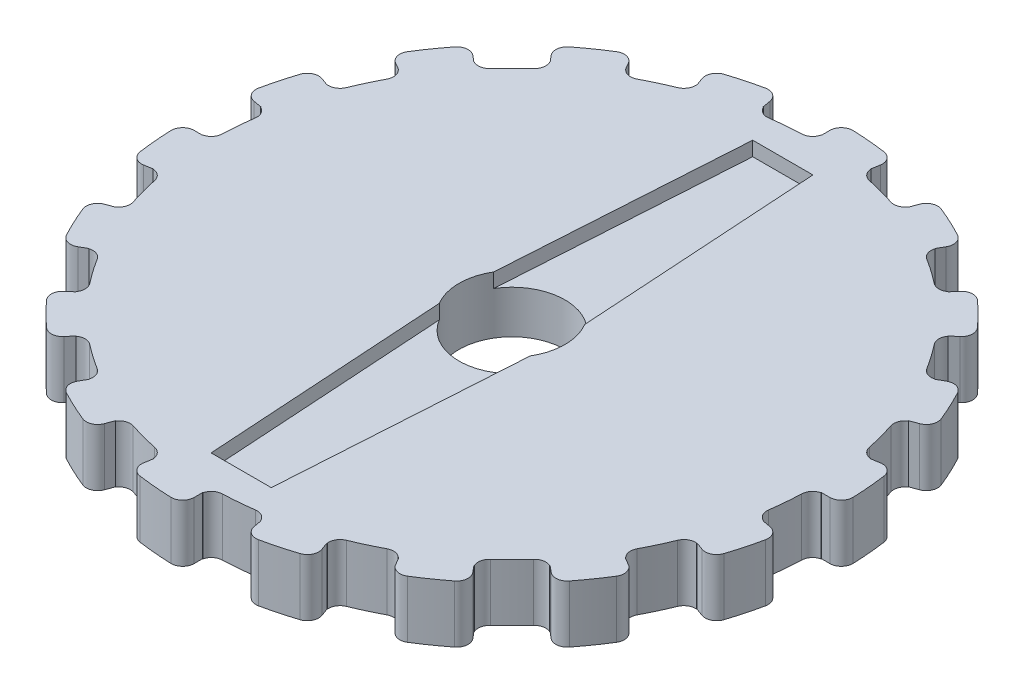
SolidWorks part; units mm, degrees
material "PLA"
ref_plane "Alzado" through (0, 0, 0) normal (0, 0, 1) x (1, 0, 0)
ref_plane "Planta" through (0, 0, 0) normal (0, 1, 0) x (1, 0, 0)
ref_plane "Vista lateral" through (0, 0, 0) normal (1, 0, 0) x (0, 0, -1)
sketch "Croquis1" plane through (0, 0, 0) normal (0, 1, 0) x (1, 0, 0)
  line L0 (0, 0) -> (0, 24) construction
  line L1 (0, 0) -> (4.1676, 23.6354) construction
  line L2 (0, 0) -> (8.2085, 22.5526) construction
  line L3 (0, 0) -> (12, 20.7846) construction
  line L4 (0, 0) -> (15.4269, 18.3851) construction
  line L5 (0, 0) -> (18.3851, 15.4269) construction
  line L6 (0, 0) -> (20.7846, 12) construction
  line L7 (0, 0) -> (22.5526, 8.2085) construction
  line L8 (0, 0) -> (23.6354, 4.1676) construction
  line L9 (0, 0) -> (24, 0) construction
  line L10 (0, 0) -> (23.6354, -4.1676) construction
  line L11 (0, 0) -> (22.5526, -8.2085) construction
  line L12 (0, 0) -> (20.7846, -12) construction
  line L13 (0, 0) -> (18.3851, -15.4269) construction
  line L14 (0, 0) -> (15.4269, -18.3851) construction
  line L15 (0, 0) -> (12, -20.7846) construction
  line L16 (0, 0) -> (8.2085, -22.5526) construction
  line L17 (0, 0) -> (4.1676, -23.6354) construction
  line L18 (0, 0) -> (0, -24) construction
  line L19 (0, 0) -> (-4.1676, -23.6354) construction
  line L20 (0, 0) -> (-8.2085, -22.5526) construction
  line L21 (0, 0) -> (-12, -20.7846) construction
  line L22 (0, 0) -> (-15.4269, -18.3851) construction
  line L23 (0, 0) -> (-18.3851, -15.4269) construction
  line L24 (0, 0) -> (-20.7846, -12) construction
  line L25 (0, 0) -> (-22.5526, -8.2085) construction
  line L26 (0, 0) -> (-23.6354, -4.1676) construction
  line L27 (0, 0) -> (-24, 0) construction
  line L28 (0, 0) -> (-23.6354, 4.1676) construction
  line L29 (0, 0) -> (-22.5526, 8.2085) construction
  line L30 (0, 0) -> (-20.7846, 12) construction
  line L31 (0, 0) -> (-18.3851, 15.4269) construction
  line L32 (0, 0) -> (-15.4269, 18.3851) construction
  line L33 (0, 0) -> (-12, 20.7846) construction
  line L34 (0, 0) -> (-8.2085, 22.5526) construction
  line L35 (0, 0) -> (-4.1676, 23.6354) construction
  line L36 (4.1676, 23.6354) -> (3.7508, 21.2718)
  line L37 (7.3876, 20.2974) -> (8.2085, 22.5526)
  line L38 (12, 20.7846) -> (10.8, 18.7061)
  line L39 (13.8842, 16.5466) -> (15.4269, 18.3851)
  line L40 (18.3851, 15.4269) -> (16.5466, 13.8842)
  line L41 (18.7061, 10.8) -> (20.7846, 12)
  line L42 (22.5526, 8.2085) -> (20.2974, 7.3876)
  line L43 (21.2718, 3.7508) -> (23.6354, 4.1676)
  line L44 (24, 0) -> (21.6, 0)
  line L45 (21.2718, -3.7508) -> (23.6354, -4.1676)
  line L46 (22.5526, -8.2085) -> (20.2974, -7.3876)
  line L47 (18.7061, -10.8) -> (20.7846, -12)
  line L48 (18.3851, -15.4269) -> (16.5466, -13.8842)
  line L49 (13.8842, -16.5466) -> (15.4269, -18.3851)
  line L50 (12, -20.7846) -> (10.8, -18.7061)
  line L51 (7.3876, -20.2974) -> (8.2085, -22.5526)
  line L52 (4.1676, -23.6354) -> (3.7508, -21.2718)
  line L53 (0, -21.6) -> (0, -24)
  line L54 (-4.1676, -23.6354) -> (-3.7508, -21.2718)
  line L55 (-7.3876, -20.2974) -> (-8.2085, -22.5526)
  line L56 (-12, -20.7846) -> (-10.8, -18.7061)
  line L57 (-13.8842, -16.5466) -> (-15.4269, -18.3851)
  line L58 (-18.3851, -15.4269) -> (-16.5466, -13.8842)
  line L59 (-18.7061, -10.8) -> (-20.7846, -12)
  line L60 (-22.5526, -8.2085) -> (-20.2974, -7.3876)
  line L61 (-21.2718, -3.7508) -> (-23.6354, -4.1676)
  line L62 (-24, 0) -> (-21.6, 0)
  line L63 (-21.2718, 3.7508) -> (-23.6354, 4.1676)
  line L64 (-22.5526, 8.2085) -> (-20.2974, 7.3876)
  line L65 (-18.7061, 10.8) -> (-20.7846, 12)
  line L66 (-18.3851, 15.4269) -> (-16.5466, 13.8842)
  line L67 (-13.8842, 16.5466) -> (-15.4269, 18.3851)
  line L68 (-12, 20.7846) -> (-10.8, 18.7061)
  line L69 (-7.3876, 20.2974) -> (-8.2085, 22.5526)
  line L70 (-4.1676, 23.6354) -> (-3.7508, 21.2718)
  line L71 (0, 21.6) -> (0, 24)
  circle A1 centre (0, 0) radius 3.7
  arc A2 (0, 24) -> (4.1676, 23.6354) centre (0, 0) cw
  arc A4 (3.7508, 21.2718) -> (7.3876, 20.2974) centre (0, 0) cw
  arc A5 (8.2085, 22.5526) -> (12, 20.7846) centre (0, 0) cw
  arc A6 (10.8, 18.7061) -> (13.8842, 16.5466) centre (0, 0) cw
  arc A7 (15.4269, 18.3851) -> (18.3851, 15.4269) centre (0, 0) cw
  arc A8 (16.5466, 13.8842) -> (18.7061, 10.8) centre (0, 0) cw
  arc A9 (20.7846, 12) -> (22.5526, 8.2085) centre (0, 0) cw
  arc A10 (20.2974, 7.3876) -> (21.2718, 3.7508) centre (0, 0) cw
  arc A11 (23.6354, 4.1676) -> (24, 0) centre (0, 0) cw
  arc A12 (21.6, 0) -> (21.2718, -3.7508) centre (0, 0) cw
  arc A13 (23.6354, -4.1676) -> (22.5526, -8.2085) centre (0, 0) cw
  arc A14 (20.2974, -7.3876) -> (18.7061, -10.8) centre (0, 0) cw
  arc A15 (20.7846, -12) -> (18.3851, -15.4269) centre (0, 0) cw
  arc A16 (16.5466, -13.8842) -> (13.8842, -16.5466) centre (0, 0) cw
  arc A17 (15.4269, -18.3851) -> (12, -20.7846) centre (0, 0) cw
  arc A18 (10.8, -18.7061) -> (7.3876, -20.2974) centre (0, 0) cw
  arc A19 (8.2085, -22.5526) -> (4.1676, -23.6354) centre (0, 0) cw
  arc A20 (3.7508, -21.2718) -> (0, -21.6) centre (0, 0) cw
  arc A21 (0, -24) -> (-4.1676, -23.6354) centre (0, 0) cw
  arc A22 (-3.7508, -21.2718) -> (-7.3876, -20.2974) centre (0, 0) cw
  arc A23 (-8.2085, -22.5526) -> (-12, -20.7846) centre (0, 0) cw
  arc A24 (-10.8, -18.7061) -> (-13.8842, -16.5466) centre (0, 0) cw
  arc A25 (-15.4269, -18.3851) -> (-18.3851, -15.4269) centre (0, 0) cw
  arc A26 (-16.5466, -13.8842) -> (-18.7061, -10.8) centre (0, 0) cw
  arc A27 (-20.7846, -12) -> (-22.5526, -8.2085) centre (0, 0) cw
  arc A28 (-20.2974, -7.3876) -> (-21.2718, -3.7508) centre (0, 0) cw
  arc A29 (-23.6354, -4.1676) -> (-24, 0) centre (0, 0) cw
  arc A30 (-21.6, 0) -> (-21.2718, 3.7508) centre (0, 0) cw
  arc A31 (-23.6354, 4.1676) -> (-22.5526, 8.2085) centre (0, 0) cw
  arc A32 (-20.2974, 7.3876) -> (-18.7061, 10.8) centre (0, 0) cw
  arc A33 (-20.7846, 12) -> (-18.3851, 15.4269) centre (0, 0) cw
  arc A34 (-16.5466, 13.8842) -> (-13.8842, 16.5466) centre (0, 0) cw
  arc A35 (-15.4269, 18.3851) -> (-12, 20.7846) centre (0, 0) cw
  arc A36 (-10.8, 18.7061) -> (-7.3876, 20.2974) centre (0, 0) cw
  arc A37 (-8.2085, 22.5526) -> (-4.1676, 23.6354) centre (0, 0) cw
  arc A38 (-3.7508, 21.2718) -> (0, 21.6) centre (0, 0) cw
  point P44 (0, 0)
  point P131 (0, 0)
  dimension "D1" = 10
  dimension "D3" = 18
  dimension "D2" = 18
extrude "Saliente-Extruir1" add sketch "Croquis1" along normal blind 4 contours A38 L70 A37 L69 A36 L68 A35 L67 A34 L66 A33 L65 A32 L64 A31 L63 A30 L62 A29 L61 A28 L60 A27 L59 A26 L58 A25 L57 A24 L56 A23 L55 A22 L54 A21 L53 A20 L52 A19 L51 A18 L50 A17 L49 A16 L48 A15 L47 A14 L46 A13 region at (3.2907, 0, -22.5715)
sketch "Croquis2" plane through (0, 4, 0) normal (0, 1, 0) x (1, 0, 0)
  line L0 (0, 1.9) -> (3.1749, 1.9) construction
  line L1 (-2.1, 18.9) -> (2.1, 18.9)
  line L2 (0, 0) -> (0, 1.9) construction
  line L3 (3.1749, 1.9) -> (2.1, 18.9)
  line L4 (0, 18.9) -> (0, 1.9) construction
  line L5 (-3.1749, 1.9) -> (-2.1, 18.9)
  line L6 (-2.2, 0) -> (2.2, 0) construction
  line L7 (3.1749, -1.9) -> (2.1, -18.9)
  line L8 (-2.1, -18.9) -> (2.1, -18.9)
  line L9 (-3.1749, -1.9) -> (-2.1, -18.9)
  circle A0 centre (0, 0) radius 3.7 construction
  arc A1 (3.1749, 1.9) -> (-3.1749, 1.9) centre (0, 0) ccw
  arc A2 (3.1749, -1.9) -> (-3.1749, -1.9) centre (0, 0) cw
extrude "Cortar-Extruir1" cut sketch "Croquis2" against normal blind 1
sketch "Croquis3" plane through (0, 4, 0) normal (0, 1, 0) x (1, 0, 0)
  line L0 (0, 22.1856) -> (0, 21) construction
  line L1 (3.8525, 21.8485) -> (3.783, 21.4543)
  line L2 (4.1676, 23.6354) -> (3.7508, 21.2718) construction
  line L3 (7.8665, 21.6129) -> (7.451, 20.4715) construction
  line L4 (7.3876, 20.2974) -> (8.2085, 22.5526) construction
  line L5 (7.451, 20.4715) -> (7.5879, 20.8476)
  line L6 (11.0928, 19.2133) -> (10.8927, 18.8666)
  line L7 (14.0033, 16.6885) -> (14.2606, 16.9951)
  line L8 (16.9951, 14.2606) -> (16.6885, 14.0033)
  line L9 (18.8666, 10.8927) -> (19.2133, 11.0928)
  line L10 (20.8476, 7.5879) -> (20.4715, 7.451)
  line L11 (21.4543, 3.783) -> (21.8485, 3.8525)
  line L12 (22.1856, 0) -> (21.7853, 0)
  line L13 (21.4543, -3.783) -> (21.8485, -3.8525)
  line L14 (20.8476, -7.5879) -> (20.4715, -7.451)
  line L15 (18.8666, -10.8927) -> (19.2133, -11.0928)
  line L16 (16.9951, -14.2606) -> (16.6885, -14.0033)
  line L17 (14.0033, -16.6885) -> (14.2606, -16.9951)
  line L18 (11.0928, -19.2133) -> (10.8927, -18.8666)
  line L19 (7.451, -20.4715) -> (7.5879, -20.8476)
  line L20 (3.8525, -21.8485) -> (3.783, -21.4543)
  line L21 (0, -21.7853) -> (0, -22.1856)
  line L22 (-3.8525, -21.8485) -> (-3.783, -21.4543)
  line L23 (-7.451, -20.4715) -> (-7.5879, -20.8476)
  line L24 (-11.0928, -19.2133) -> (-10.8927, -18.8666)
  line L25 (-14.0033, -16.6885) -> (-14.2606, -16.9951)
  line L26 (-16.9951, -14.2606) -> (-16.6885, -14.0033)
  line L27 (-18.8666, -10.8927) -> (-19.2133, -11.0928)
  line L28 (-20.8476, -7.5879) -> (-20.4715, -7.451)
  line L29 (-21.4543, -3.783) -> (-21.8485, -3.8525)
  line L30 (-22.1856, 0) -> (-21.7853, 0)
  line L31 (-21.4543, 3.783) -> (-21.8485, 3.8525)
  line L32 (-20.8476, 7.5879) -> (-20.4715, 7.451)
  line L33 (-18.8666, 10.8927) -> (-19.2133, 11.0928)
  line L34 (-16.9951, 14.2606) -> (-16.6885, 14.0033)
  line L35 (-14.0033, 16.6885) -> (-14.2606, 16.9951)
  line L36 (-11.0928, 19.2133) -> (-10.8927, 18.8666)
  line L37 (-7.451, 20.4715) -> (-7.5879, 20.8476)
  line L38 (-3.8525, 21.8485) -> (-3.783, 21.4543)
  line L39 (0, 21.7853) -> (0, 22.1856)
  line L40 (0, 22.1856) -> (0, 24)
  line L41 (4.1676, 23.6354) -> (3.8525, 21.8485)
  line L42 (7.5879, 20.8476) -> (8.2085, 22.5526)
  line L43 (12, 20.7846) -> (11.0928, 19.2133)
  line L44 (14.2606, 16.9951) -> (15.4269, 18.3851)
  line L45 (18.3851, 15.4269) -> (16.9951, 14.2606)
  line L46 (19.2133, 11.0928) -> (20.7846, 12)
  line L47 (22.5526, 8.2085) -> (20.8476, 7.5879)
  line L48 (21.8485, 3.8525) -> (23.6354, 4.1676)
  line L49 (24, 0) -> (22.1856, 0)
  line L50 (21.8485, -3.8525) -> (23.6354, -4.1676)
  line L51 (22.5526, -8.2085) -> (20.8476, -7.5879)
  line L52 (19.2133, -11.0928) -> (20.7846, -12)
  line L53 (18.3851, -15.4269) -> (16.9951, -14.2606)
  line L54 (14.2606, -16.9951) -> (15.4269, -18.3851)
  line L55 (12, -20.7846) -> (11.0928, -19.2133)
  line L56 (7.5879, -20.8476) -> (8.2085, -22.5526)
  line L57 (4.1676, -23.6354) -> (3.8525, -21.8485)
  line L58 (0, -22.1856) -> (0, -24)
  line L59 (-4.1676, -23.6354) -> (-3.8525, -21.8485)
  line L60 (-7.5879, -20.8476) -> (-8.2085, -22.5526)
  line L61 (-12, -20.7846) -> (-11.0928, -19.2133)
  line L62 (-14.2606, -16.9951) -> (-15.4269, -18.3851)
  line L63 (-18.3851, -15.4269) -> (-16.9951, -14.2606)
  line L64 (-19.2133, -11.0928) -> (-20.7846, -12)
  line L65 (-22.5526, -8.2085) -> (-20.8476, -7.5879)
  line L66 (-21.8485, -3.8525) -> (-23.6354, -4.1676)
  line L67 (-24, 0) -> (-22.1856, 0)
  line L68 (-21.8485, 3.8525) -> (-23.6354, 4.1676)
  line L69 (-22.5526, 8.2085) -> (-20.8476, 7.5879)
  line L70 (-19.2133, 11.0928) -> (-20.7846, 12)
  line L71 (-18.3851, 15.4269) -> (-16.9951, 14.2606)
  line L72 (-14.2606, 16.9951) -> (-15.4269, 18.3851)
  line L73 (-12, 20.7846) -> (-11.0928, 19.2133)
  line L74 (-7.5879, 20.8476) -> (-8.2085, 22.5526)
  line L75 (-4.1676, 23.6354) -> (-3.8525, 21.8485)
  circle A0 centre (0, 0) radius 23 construction
  circle A1 centre (0, 0) radius 21 construction
  arc A2 (0.8288, 22.9851) -> (3.1751, 22.7798) centre (0, 0) cw
  arc A3 (4.4031, 20.5332) -> (6.4534, 19.9838) centre (0, 0) cw
  arc A4 (7.451, 20.4715) -> (6.4534, 19.9838) centre (6.6993, 20.7451) cw
  arc A5 (3.783, 21.4543) -> (4.4031, 20.5332) centre (4.5708, 21.3154) ccw
  arc A6 (3.8525, 21.8485) -> (3.1751, 22.7798) centre (3.0646, 21.9875) ccw
  arc A7 (0, 22.1856) -> (0.8288, 22.9851) centre (0.8, 22.1856) cw
  arc A8 (8.6402, 21.3154) -> (11.506, 19.9151) centre (0, 0) cw construction
  arc A9 (7.5879, 20.8476) -> (8.6402, 21.3154) centre (8.3397, 20.574) cw construction
  arc A10 (7.5879, 20.8476) -> (8.6402, 21.3154) centre (8.3397, 20.574) cw
  arc A11 (8.6402, 21.3154) -> (10.7747, 20.3201) centre (0, 0) cw
  arc A12 (11.0928, 19.2133) -> (10.7747, 20.3201) centre (10.4, 19.6133) ccw
  arc A13 (10.8927, 18.8666) -> (11.1603, 17.789) centre (11.5855, 18.4666) ccw
  arc A14 (11.1603, 17.789) -> (12.8991, 16.5715) centre (0, 0) cw
  arc A15 (14.0033, 16.6885) -> (12.8991, 16.5715) centre (13.3905, 17.2028) cw
  arc A16 (14.2606, 16.9951) -> (15.4094, 17.0748) centre (14.8735, 16.4809) cw
  arc A17 (15.4094, 17.0748) -> (17.0748, 15.4094) centre (0, 0) cw
  arc A18 (16.9951, 14.2606) -> (17.0748, 15.4094) centre (16.4809, 14.8735) ccw
  arc A19 (16.6885, 14.0033) -> (16.5715, 12.8991) centre (17.2028, 13.3905) ccw
  arc A20 (16.5715, 12.8991) -> (17.789, 11.1603) centre (0, 0) cw
  arc A21 (18.8666, 10.8927) -> (17.789, 11.1603) centre (18.4666, 11.5855) cw
  arc A22 (19.2133, 11.0928) -> (20.3201, 10.7747) centre (19.6133, 10.4) cw
  arc A23 (20.3201, 10.7747) -> (21.3154, 8.6402) centre (0, 0) cw
  arc A24 (20.8476, 7.5879) -> (21.3154, 8.6402) centre (20.574, 8.3397) ccw
  arc A25 (20.4715, 7.451) -> (19.9838, 6.4534) centre (20.7451, 6.6993) ccw
  arc A26 (19.9838, 6.4534) -> (20.5332, 4.4031) centre (0, 0) cw
  arc A27 (21.4543, 3.783) -> (20.5332, 4.4031) centre (21.3154, 4.5708) cw
  arc A28 (21.8485, 3.8525) -> (22.7798, 3.1751) centre (21.9875, 3.0646) cw
  arc A29 (22.7798, 3.1751) -> (22.9851, 0.8288) centre (0, 0) cw
  arc A30 (22.1856, 0) -> (22.9851, 0.8288) centre (22.1856, 0.8) ccw
  arc A31 (21.7853, 0) -> (20.9859, -0.7706) centre (21.7853, -0.8) ccw
  arc A32 (20.9859, -0.7706) -> (20.8009, -2.8852) centre (0, 0) cw
  arc A33 (21.4543, -3.783) -> (20.8009, -2.8852) centre (21.5933, -2.9951) cw
  arc A34 (21.8485, -3.8525) -> (22.4919, -4.8076) centre (21.7096, -4.6403) cw
  arc A35 (22.4919, -4.8076) -> (21.8824, -7.0825) centre (0, 0) cw
  arc A36 (20.8476, -7.5879) -> (21.8824, -7.0825) centre (21.1212, -6.8362) ccw
  arc A37 (20.4715, -7.451) -> (19.4567, -7.9018) centre (20.1979, -8.2028) ccw
  arc A38 (19.4567, -7.9018) -> (18.5596, -9.8255) centre (0, 0) cw
  arc A39 (18.8666, -10.8927) -> (18.5596, -9.8255) centre (19.2666, -10.1998) cw
  arc A40 (19.2133, -11.0928) -> (19.4912, -12.2103) centre (18.8133, -11.7856) cw
  arc A41 (19.4912, -12.2103) -> (18.1403, -14.1396) centre (0, 0) cw
  arc A42 (16.9951, -14.2606) -> (18.1403, -14.1396) centre (17.5094, -13.6478) ccw
  arc A43 (16.6885, -14.0033) -> (15.5807, -14.0798) centre (16.1743, -14.6162) ccw
  arc A44 (15.5807, -14.0798) -> (14.0798, -15.5807) centre (0, 0) cw
  arc A45 (14.0033, -16.6885) -> (14.0798, -15.5807) centre (14.6162, -16.1743) cw
  arc A46 (14.2606, -16.9951) -> (14.1396, -18.1403) centre (13.6478, -17.5094) cw
  arc A47 (14.1396, -18.1403) -> (12.2103, -19.4912) centre (0, 0) cw
  arc A48 (11.0928, -19.2133) -> (12.2103, -19.4912) centre (11.7856, -18.8133) ccw
  arc A49 (10.8927, -18.8666) -> (9.8255, -18.5596) centre (10.1998, -19.2666) ccw
  arc A50 (9.8255, -18.5596) -> (7.9018, -19.4567) centre (0, 0) cw
  arc A51 (7.451, -20.4715) -> (7.9018, -19.4567) centre (8.2028, -20.1979) cw
  arc A52 (7.5879, -20.8476) -> (7.0825, -21.8824) centre (6.8362, -21.1212) cw
  arc A53 (7.0825, -21.8824) -> (4.8076, -22.4919) centre (0, 0) cw
  arc A54 (3.8525, -21.8485) -> (4.8076, -22.4919) centre (4.6403, -21.7096) ccw
  arc A55 (3.783, -21.4543) -> (2.8852, -20.8009) centre (2.9951, -21.5933) ccw
  arc A56 (2.8852, -20.8009) -> (0.7706, -20.9859) centre (0, 0) cw
  arc A57 (0, -21.7853) -> (0.7706, -20.9859) centre (0.8, -21.7853) cw
  arc A58 (0, -22.1856) -> (-0.8288, -22.9851) centre (-0.8, -22.1856) cw
  arc A59 (-0.8288, -22.9851) -> (-3.1751, -22.7798) centre (0, 0) cw
  arc A60 (-3.8525, -21.8485) -> (-3.1751, -22.7798) centre (-3.0646, -21.9875) ccw
  arc A61 (-3.783, -21.4543) -> (-4.4031, -20.5332) centre (-4.5708, -21.3154) ccw
  arc A62 (-4.4031, -20.5332) -> (-6.4534, -19.9838) centre (0, 0) cw
  arc A63 (-7.451, -20.4715) -> (-6.4534, -19.9838) centre (-6.6993, -20.7451) cw
  arc A64 (-7.5879, -20.8476) -> (-8.6402, -21.3154) centre (-8.3397, -20.574) cw
  arc A65 (-8.6402, -21.3154) -> (-10.7747, -20.3201) centre (0, 0) cw
  arc A66 (-11.0928, -19.2133) -> (-10.7747, -20.3201) centre (-10.4, -19.6133) ccw
  arc A67 (-10.8927, -18.8666) -> (-11.1603, -17.789) centre (-11.5855, -18.4666) ccw
  arc A68 (-11.1603, -17.789) -> (-12.8991, -16.5715) centre (0, 0) cw
  arc A69 (-14.0033, -16.6885) -> (-12.8991, -16.5715) centre (-13.3905, -17.2028) cw
  arc A70 (-14.2606, -16.9951) -> (-15.4094, -17.0748) centre (-14.8735, -16.4809) cw
  arc A71 (-15.4094, -17.0748) -> (-17.0748, -15.4094) centre (0, 0) cw
  arc A72 (-16.9951, -14.2606) -> (-17.0748, -15.4094) centre (-16.4809, -14.8735) ccw
  arc A73 (-16.6885, -14.0033) -> (-16.5715, -12.8991) centre (-17.2028, -13.3905) ccw
  arc A74 (-16.5715, -12.8991) -> (-17.789, -11.1603) centre (0, 0) cw
  arc A75 (-18.8666, -10.8927) -> (-17.789, -11.1603) centre (-18.4666, -11.5855) cw
  arc A76 (-19.2133, -11.0928) -> (-20.3201, -10.7747) centre (-19.6133, -10.4) cw
  arc A77 (-20.3201, -10.7747) -> (-21.3154, -8.6402) centre (0, 0) cw
  arc A78 (-20.8476, -7.5879) -> (-21.3154, -8.6402) centre (-20.574, -8.3397) ccw
  arc A79 (-20.4715, -7.451) -> (-19.9838, -6.4534) centre (-20.7451, -6.6993) ccw
  arc A80 (-19.9838, -6.4534) -> (-20.5332, -4.4031) centre (0, 0) cw
  arc A81 (-21.4543, -3.783) -> (-20.5332, -4.4031) centre (-21.3154, -4.5708) cw
  arc A82 (-21.8485, -3.8525) -> (-22.7798, -3.1751) centre (-21.9875, -3.0646) cw
  arc A83 (-22.7798, -3.1751) -> (-22.9851, -0.8288) centre (0, 0) cw
  arc A84 (-22.1856, 0) -> (-22.9851, -0.8288) centre (-22.1856, -0.8) ccw
  arc A85 (-21.7853, 0) -> (-20.9859, 0.7706) centre (-21.7853, 0.8) ccw
  arc A86 (-20.9859, 0.7706) -> (-20.8009, 2.8852) centre (0, 0) cw
  arc A87 (-21.4543, 3.783) -> (-20.8009, 2.8852) centre (-21.5933, 2.9951) cw
  arc A88 (-21.8485, 3.8525) -> (-22.4919, 4.8076) centre (-21.7096, 4.6403) cw
  arc A89 (-22.4919, 4.8076) -> (-21.8824, 7.0825) centre (0, 0) cw
  arc A90 (-20.8476, 7.5879) -> (-21.8824, 7.0825) centre (-21.1212, 6.8362) ccw
  arc A91 (-20.4715, 7.451) -> (-19.4567, 7.9018) centre (-20.1979, 8.2028) ccw
  arc A92 (-19.4567, 7.9018) -> (-18.5596, 9.8255) centre (0, 0) cw
  arc A93 (-18.8666, 10.8927) -> (-18.5596, 9.8255) centre (-19.2666, 10.1998) cw
  arc A94 (-19.2133, 11.0928) -> (-19.4912, 12.2103) centre (-18.8133, 11.7856) cw
  arc A95 (-19.4912, 12.2103) -> (-18.1403, 14.1396) centre (0, 0) cw
  arc A96 (-16.9951, 14.2606) -> (-18.1403, 14.1396) centre (-17.5094, 13.6478) ccw
  arc A97 (-16.6885, 14.0033) -> (-15.5807, 14.0798) centre (-16.1743, 14.6162) ccw
  arc A98 (-15.5807, 14.0798) -> (-14.0798, 15.5807) centre (0, 0) cw
  arc A99 (-14.0033, 16.6885) -> (-14.0798, 15.5807) centre (-14.6162, 16.1743) cw
  arc A100 (-14.2606, 16.9951) -> (-14.1396, 18.1403) centre (-13.6478, 17.5094) cw
  arc A101 (-14.1396, 18.1403) -> (-12.2103, 19.4912) centre (0, 0) cw
  arc A102 (-11.0928, 19.2133) -> (-12.2103, 19.4912) centre (-11.7856, 18.8133) ccw
  arc A103 (-10.8927, 18.8666) -> (-9.8255, 18.5596) centre (-10.1998, 19.2666) ccw
  arc A104 (-9.8255, 18.5596) -> (-7.9018, 19.4567) centre (0, 0) cw
  arc A105 (-7.451, 20.4715) -> (-7.9018, 19.4567) centre (-8.2028, 20.1979) cw
  arc A106 (-7.5879, 20.8476) -> (-7.0825, 21.8824) centre (-6.8362, 21.1212) cw
  arc A107 (-7.0825, 21.8824) -> (-4.8076, 22.4919) centre (0, 0) cw
  arc A108 (-3.8525, 21.8485) -> (-4.8076, 22.4919) centre (-4.6403, 21.7096) ccw
  arc A109 (-3.783, 21.4543) -> (-2.8852, 20.8009) centre (-2.9951, 21.5933) ccw
  arc A110 (-2.8852, 20.8009) -> (-0.7706, 20.9859) centre (0, 0) cw
  arc A111 (0, 21.7853) -> (-0.7706, 20.9859) centre (-0.8, 21.7853) cw
  arc A112 (0, 24) -> (4.1676, 23.6354) centre (0, 0) cw
  arc A113 (3.7508, 21.2718) -> (7.3876, 20.2974) centre (0, 0) cw
  arc A114 (8.2085, 22.5526) -> (12, 20.7846) centre (0, 0) cw
  arc A115 (10.8, 18.7061) -> (13.8842, 16.5466) centre (0, 0) cw
  arc A116 (15.4269, 18.3851) -> (18.3851, 15.4269) centre (0, 0) cw
  arc A117 (16.5466, 13.8842) -> (18.7061, 10.8) centre (0, 0) cw
  arc A118 (20.7846, 12) -> (22.5526, 8.2085) centre (0, 0) cw
  arc A119 (20.2974, 7.3876) -> (21.2718, 3.7508) centre (0, 0) cw
  arc A120 (23.6354, 4.1676) -> (24, 0) centre (0, 0) cw
  arc A121 (21.6, 0) -> (21.2718, -3.7508) centre (0, 0) cw
  arc A122 (23.6354, -4.1676) -> (22.5526, -8.2085) centre (0, 0) cw
  arc A123 (20.2974, -7.3876) -> (18.7061, -10.8) centre (0, 0) cw
  arc A124 (20.7846, -12) -> (18.3851, -15.4269) centre (0, 0) cw
  arc A125 (16.5466, -13.8842) -> (13.8842, -16.5466) centre (0, 0) cw
  arc A126 (15.4269, -18.3851) -> (12, -20.7846) centre (0, 0) cw
  arc A127 (10.8, -18.7061) -> (7.3876, -20.2974) centre (0, 0) cw
  arc A128 (8.2085, -22.5526) -> (4.1676, -23.6354) centre (0, 0) cw
  arc A129 (3.7508, -21.2718) -> (0, -21.6) centre (0, 0) cw
  arc A130 (0, -24) -> (-4.1676, -23.6354) centre (0, 0) cw
  arc A131 (-3.7508, -21.2718) -> (-7.3876, -20.2974) centre (0, 0) cw
  arc A132 (-8.2085, -22.5526) -> (-12, -20.7846) centre (0, 0) cw
  arc A133 (-10.8, -18.7061) -> (-13.8842, -16.5466) centre (0, 0) cw
  arc A134 (-15.4269, -18.3851) -> (-18.3851, -15.4269) centre (0, 0) cw
  arc A135 (-16.5466, -13.8842) -> (-18.7061, -10.8) centre (0, 0) cw
  arc A136 (-20.7846, -12) -> (-22.5526, -8.2085) centre (0, 0) cw
  arc A137 (-20.2974, -7.3876) -> (-21.2718, -3.7508) centre (0, 0) cw
  arc A138 (-23.6354, -4.1676) -> (-24, 0) centre (0, 0) cw
  arc A139 (-21.6, 0) -> (-21.2718, 3.7508) centre (0, 0) cw
  arc A140 (-23.6354, 4.1676) -> (-22.5526, 8.2085) centre (0, 0) cw
  arc A141 (-20.2974, 7.3876) -> (-18.7061, 10.8) centre (0, 0) cw
  arc A142 (-20.7846, 12) -> (-18.3851, 15.4269) centre (0, 0) cw
  arc A143 (-16.5466, 13.8842) -> (-13.8842, 16.5466) centre (0, 0) cw
  arc A144 (-15.4269, 18.3851) -> (-12, 20.7846) centre (0, 0) cw
  arc A145 (-10.8, 18.7061) -> (-7.3876, 20.2974) centre (0, 0) cw
  arc A146 (-8.2085, 22.5526) -> (-4.1676, 23.6354) centre (0, 0) cw
  arc A147 (-3.7508, 21.2718) -> (0, 21.6) centre (0, 0) cw
  point P18 (7.1824, 19.7335)
  point P21 (3.6466, 20.681)
  point P24 (3.9939, 22.6506)
  point P27 (0, 23)
  point P257 (0, 0)
  point P369 (0, 0)
  dimension "D1" = 0.8
  dimension "D2" = 0.8
  dimension "D3" = 18
  dimension "D4" = 18
extrude "Cortar-Extruir2" cut sketch "Croquis3" against normal blind 4 contours A112 L40 A7 A2 A6 L41 | A113 A5 A3 A4 region at (2.0417, 4, -23.3365) region at (5.512, 4, -20.5709)
pattern_circular "MatrizC1" count 18 every 20 about axis through (0, 4, 0) along (0, -1, 0) of "Cortar-Extruir2"
scale "Escala1" scale about centroid uniform scaling yes scale factor 0.99
sketch "Croquis4" plane through (0, 3.9796, 0) normal (0, 1, 0) x (1, 0, 0)
  point P0 (0, 0)
ref_axis "Eje1" through (0, 0, 0) along (0, 1, 0)
